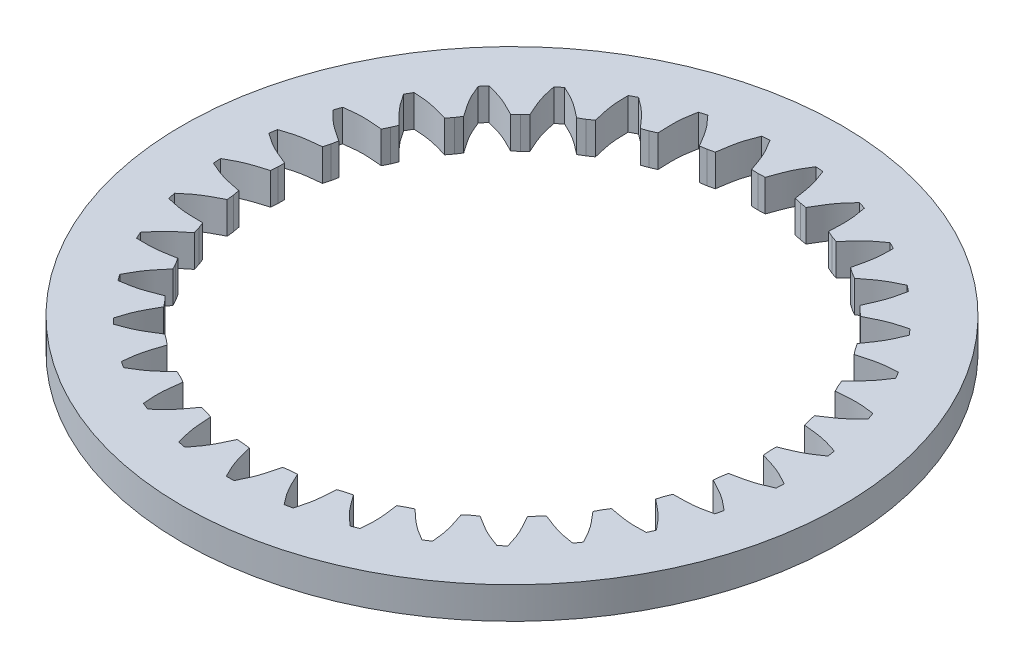
SolidWorks part; units mm, degrees
ref_plane "Plano frontal" through (0, 0, 0) normal (0, 0, 1) x (1, 0, 0)
ref_plane "Plano superior" through (0, 0, 0) normal (0, 1, 0) x (1, 0, 0)
ref_plane "Plano direito" through (0, 0, 0) normal (1, 0, 0) x (0, 0, -1)
sketch "Esboço1" plane through (0, 0, 0) normal (0, 1, 0) x (1, 0, 0)
  line L0 (-38.3259, -48.7353) -> (0, 0)
  line L1 (-39.711, -47.7305) -> (-38.3259, -48.7353)
  line L2 (-38.3259, -48.7353) -> (-37.0229, -49.8445)
  line L3 (-39.1966, -59.1999) -> (-37.5673, -60.247)
  line L4 (-27.2846, -65.5481) -> (-25.4866, -66.2679)
  line L5 (-28.41, -55.1078) -> (-26.9207, -55.9504)
  line L6 (-29.9603, -54.3833) -> (-28.41, -55.1078)
  line L7 (-14.3865, -69.5272) -> (-12.4847, -69.8937)
  line L8 (-17.4674, -59.4886) -> (-15.8455, -60.0341)
  line L9 (-19.1268, -59.0706) -> (-17.4674, -59.4886)
  line L10 (-0.9684, -70.9934) -> (0.9684, -70.9934)
  line L11 (-5.8935, -61.7193) -> (-4.1976, -61.9479)
  line L12 (-7.6019, -61.6229) -> (-5.8935, -61.7193)
  line L13 (12.4847, -69.8937) -> (14.3865, -69.5272)
  line L14 (5.8935, -61.7193) -> (7.6019, -61.6229)
  line L15 (4.1976, -61.9479) -> (5.8935, -61.7193)
  line L16 (25.4866, -66.2679) -> (27.2846, -65.5481)
  line L17 (17.4674, -59.4886) -> (19.1268, -59.0706)
  line L18 (15.8455, -60.0341) -> (17.4674, -59.4886)
  line L19 (37.5673, -60.247) -> (39.1966, -59.1999)
  line L20 (28.41, -55.1078) -> (29.9603, -54.3833)
  line L21 (26.9207, -55.9504) -> (28.41, -55.1078)
  line L22 (48.2902, -52.0486) -> (49.6919, -50.7121)
  line L23 (38.3259, -48.7353) -> (39.711, -47.7305)
  line L24 (37.0229, -49.8445) -> (38.3259, -48.7353)
  line L25 (57.2678, -41.969) -> (58.3912, -40.3914)
  line L26 (46.8565, -40.6014) -> (48.0264, -39.3526)
  line L27 (45.7869, -41.9371) -> (46.8565, -40.6014)
  line L28 (64.1756, -30.3726) -> (64.9801, -28.6109)
  line L29 (53.6936, -31) -> (54.6061, -29.5524)
  line L30 (52.8962, -32.514) -> (53.6936, -31)
  line L31 (68.7639, -17.6784) -> (69.2205, -15.7962)
  line L32 (58.59, -20.2782) -> (59.2121, -18.6841)
  line L33 (58.0936, -21.9158) -> (58.59, -20.2782)
  line L34 (70.8669, -4.3453) -> (70.9591, -2.4107)
  line L35 (61.3689, -8.8235) -> (61.678, -7.1405)
  line L36 (61.1914, -10.5255) -> (61.3689, -8.8235)
  line L37 (70.4086, 9.1449) -> (70.133, 11.0619)
  line L38 (61.9298, 2.9501) -> (61.9148, 4.6612)
  line L39 (62.0775, 1.2453) -> (61.9298, 2.9501)
  line L40 (67.4055, 22.3045) -> (66.7721, 24.1348)
  line L41 (60.2523, 14.6171) -> (59.9138, 16.2944)
  line L42 (60.72, 12.971) -> (60.2523, 14.6171)
  line L43 (61.9663, 34.6581) -> (60.9979, 36.3353)
  line L44 (56.3972, 25.7557) -> (55.7473, 27.3387)
  line L45 (57.1679, 24.228) -> (56.3972, 25.7557)
  line L46 (54.2874, 45.7589) -> (53.0191, 47.2226)
  line L47 (50.5037, 35.9635) -> (49.566, 37.3949)
  line L48 (51.5497, 34.6092) -> (50.5037, 35.9635)
  line L49 (44.6464, 55.206) -> (43.124, 56.4032)
  line L50 (42.7849, 44.8715) -> (41.5932, 46.0996)
  line L51 (44.0683, 43.7396) -> (42.7849, 44.8715)
  line L52 (33.3918, 62.6577) -> (31.6703, 63.5452)
  line L53 (33.5197, 52.1577) -> (32.1172, 53.1381)
  line L54 (34.9941, 51.2892) -> (33.5197, 52.1577)
  line L55 (20.9303, 67.8448) -> (19.072, 68.3905)
  line L56 (23.0431, 57.5588) -> (21.4804, 58.256)
  line L57 (24.6552, 56.985) -> (23.0431, 57.5588)
  line L58 (7.7123, 70.5799) -> (5.7844, 70.764)
  line L59 (11.7336, 60.8796) -> (10.0672, 61.2684)
  line L60 (13.4252, 60.6212) -> (11.7336, 60.8796)
  line L61 (-5.7844, 70.764) -> (-7.7123, 70.5799)
  line L62 (0, 62) -> (-1.7099, 62.0665)
  line L63 (1.7099, 62.0665) -> (0, 62)
  line L64 (-19.072, 68.3905) -> (-20.9303, 67.8448)
  line L65 (-11.7336, 60.8796) -> (-13.4251, 60.6212)
  line L66 (-10.0672, 61.2684) -> (-11.7336, 60.8796)
  line L67 (-31.6703, 63.5452) -> (-33.3918, 62.6577)
  line L68 (-23.0431, 57.5588) -> (-24.6552, 56.985)
  line L69 (-21.4804, 58.256) -> (-23.0431, 57.5588)
  line L70 (-43.124, 56.4032) -> (-44.6464, 55.206)
  line L71 (-33.5197, 52.1577) -> (-34.9941, 51.2892)
  line L72 (-32.1172, 53.1381) -> (-33.5197, 52.1577)
  line L73 (-53.0191, 47.2226) -> (-54.2874, 45.7589)
  line L74 (-42.7849, 44.8715) -> (-44.0683, 43.7396)
  line L75 (-41.5932, 46.0996) -> (-42.7849, 44.8715)
  line L76 (-60.9979, 36.3353) -> (-61.9663, 34.6581)
  line L77 (-50.5037, 35.9635) -> (-51.5497, 34.6092)
  line L78 (-49.566, 37.3949) -> (-50.5037, 35.9635)
  line L79 (-66.7721, 24.1348) -> (-67.4055, 22.3045)
  line L80 (-56.3972, 25.7557) -> (-57.1679, 24.228)
  line L81 (-55.7473, 27.3387) -> (-56.3972, 25.7557)
  line L82 (-70.133, 11.0619) -> (-70.4086, 9.1449)
  line L83 (-60.2523, 14.6171) -> (-60.72, 12.971)
  line L84 (-59.9138, 16.2944) -> (-60.2523, 14.6171)
  line L85 (-70.9591, -2.4107) -> (-70.8669, -4.3453)
  line L86 (-61.9298, 2.9501) -> (-62.0775, 1.2453)
  line L87 (-61.9148, 4.6612) -> (-61.9298, 2.9501)
  line L88 (-69.2205, -15.7962) -> (-68.7639, -17.6784)
  line L89 (-61.3689, -8.8235) -> (-61.1914, -10.5255)
  line L90 (-61.678, -7.1405) -> (-61.3689, -8.8235)
  line L91 (-64.9801, -28.6108) -> (-64.1756, -30.3726)
  line L92 (-58.5901, -20.2782) -> (-58.0936, -21.9158)
  line L93 (-59.2121, -18.6841) -> (-58.5901, -20.2782)
  line L94 (-58.3912, -40.3914) -> (-57.2678, -41.969)
  line L95 (-53.6936, -31) -> (-52.8962, -32.514)
  line L96 (-54.6061, -29.5524) -> (-53.6936, -31)
  line L97 (-49.6919, -50.7121) -> (-48.2902, -52.0486)
  line L98 (-46.8565, -40.6014) -> (-45.787, -41.9371)
  line L99 (-48.0264, -39.3526) -> (-46.8565, -40.6014)
  circle A0 centre (0, 0) radius 83
  spline S0 degree 3 number of poles 788 (-39.1966, -59.1999) -> (-37.0229, -49.8445)
  spline S1 degree 3 number of poles 788 (-48.2902, -52.0486) -> (-39.711, -47.7305)
  spline S2 degree 3 number of poles 788 (-27.2846, -65.5481) -> (-26.9207, -55.9504)
  spline S3 degree 3 number of poles 788 (-37.5673, -60.247) -> (-29.9603, -54.3833)
  spline S4 degree 3 number of poles 788 (-14.3865, -69.5272) -> (-15.8455, -60.0341)
  spline S5 degree 3 number of poles 788 (-25.4866, -66.2679) -> (-19.1268, -59.0706)
  spline S6 degree 3 number of poles 788 (-0.9684, -70.9934) -> (-4.1976, -61.9479)
  spline S7 degree 3 number of poles 788 (-12.4847, -69.8937) -> (-7.6019, -61.6229)
  spline S8 degree 3 number of poles 788 (12.4847, -69.8937) -> (7.6019, -61.6229)
  spline S9 degree 3 number of poles 788 (0.9684, -70.9934) -> (4.1976, -61.9479)
  spline S10 degree 3 number of poles 788 (25.4866, -66.2679) -> (19.1268, -59.0706)
  spline S11 degree 3 number of poles 788 (14.3865, -69.5272) -> (15.8455, -60.0341)
  spline S12 degree 3 number of poles 788 (37.5673, -60.247) -> (29.9603, -54.3833)
  spline S13 degree 3 number of poles 788 (27.2846, -65.5481) -> (26.9207, -55.9504)
  spline S14 degree 3 number of poles 788 (48.2902, -52.0486) -> (39.711, -47.7305)
  spline S15 degree 3 number of poles 788 (39.1966, -59.1999) -> (37.0229, -49.8445)
  spline S16 degree 3 number of poles 788 (57.2678, -41.969) -> (48.0264, -39.3526)
  spline S17 degree 3 number of poles 788 (49.6919, -50.7121) -> (45.7869, -41.9371)
  spline S18 degree 3 number of poles 788 (64.1756, -30.3726) -> (54.6061, -29.5524)
  spline S19 degree 3 number of poles 788 (58.3912, -40.3914) -> (52.8962, -32.514)
  spline S20 degree 3 number of poles 788 (68.7639, -17.6784) -> (59.2121, -18.6841)
  spline S21 degree 3 number of poles 788 (64.9801, -28.6109) -> (58.0936, -21.9158)
  spline S22 degree 3 number of poles 788 (70.8669, -4.3453) -> (61.678, -7.1405)
  spline S23 degree 3 number of poles 788 (69.2205, -15.7962) -> (61.1914, -10.5255)
  spline S24 degree 3 number of poles 788 (70.4086, 9.1449) -> (61.9148, 4.6612)
  spline S25 degree 3 number of poles 788 (70.9591, -2.4107) -> (62.0775, 1.2453)
  spline S26 degree 3 number of poles 788 (67.4055, 22.3045) -> (59.9138, 16.2944)
  spline S27 degree 3 number of poles 788 (70.133, 11.0619) -> (60.72, 12.971)
  spline S28 degree 3 number of poles 788 (61.9663, 34.6581) -> (55.7473, 27.3387)
  spline S29 degree 3 number of poles 788 (66.7721, 24.1348) -> (57.1679, 24.228)
  spline S30 degree 3 number of poles 788 (54.2874, 45.7589) -> (49.566, 37.3949)
  spline S31 degree 3 number of poles 788 (60.9979, 36.3353) -> (51.5497, 34.6092)
  spline S32 degree 3 number of poles 788 (44.6464, 55.206) -> (41.5932, 46.0996)
  spline S33 degree 3 number of poles 788 (53.0191, 47.2226) -> (44.0683, 43.7396)
  spline S34 degree 3 number of poles 788 (33.3918, 62.6577) -> (32.1172, 53.1381)
  spline S35 degree 3 number of poles 788 (43.124, 56.4032) -> (34.9941, 51.2892)
  spline S36 degree 3 number of poles 788 (20.9303, 67.8448) -> (21.4804, 58.256)
  spline S37 degree 3 number of poles 788 (31.6703, 63.5452) -> (24.6552, 56.985)
  spline S38 degree 3 number of poles 788 (7.7123, 70.5799) -> (10.0672, 61.2684)
  spline S39 degree 3 number of poles 788 (19.072, 68.3905) -> (13.4252, 60.6212)
  spline S40 degree 3 number of poles 788 (-5.7844, 70.764) -> (-1.7099, 62.0665)
  spline S41 degree 3 number of poles 788 (5.7844, 70.764) -> (1.7099, 62.0665)
  spline S42 degree 3 number of poles 788 (-19.072, 68.3905) -> (-13.4251, 60.6212)
  spline S43 degree 3 number of poles 788 (-7.7123, 70.5799) -> (-10.0672, 61.2684)
  spline S44 degree 3 number of poles 788 (-31.6703, 63.5452) -> (-24.6552, 56.985)
  spline S45 degree 3 number of poles 788 (-20.9303, 67.8448) -> (-21.4804, 58.256)
  spline S46 degree 3 number of poles 788 (-43.124, 56.4032) -> (-34.9941, 51.2892)
  spline S47 degree 3 number of poles 788 (-33.3918, 62.6577) -> (-32.1172, 53.1381)
  spline S48 degree 3 number of poles 788 (-53.0191, 47.2226) -> (-44.0683, 43.7396)
  spline S49 degree 3 number of poles 788 (-44.6464, 55.206) -> (-41.5932, 46.0996)
  spline S50 degree 3 number of poles 788 (-60.9979, 36.3353) -> (-51.5497, 34.6092)
  spline S51 degree 3 number of poles 788 (-54.2874, 45.7589) -> (-49.566, 37.3949)
  spline S52 degree 3 number of poles 788 (-66.7721, 24.1348) -> (-57.1679, 24.228)
  spline S53 degree 3 number of poles 788 (-61.9663, 34.6581) -> (-55.7473, 27.3387)
  spline S54 degree 3 number of poles 788 (-70.133, 11.0619) -> (-60.72, 12.971)
  spline S55 degree 3 number of poles 788 (-67.4055, 22.3045) -> (-59.9138, 16.2944)
  spline S56 degree 3 number of poles 788 (-70.9591, -2.4107) -> (-62.0775, 1.2453)
  spline S57 degree 3 number of poles 788 (-70.4086, 9.1449) -> (-61.9148, 4.6612)
  spline S58 degree 3 number of poles 788 (-69.2205, -15.7962) -> (-61.1914, -10.5255)
  spline S59 degree 3 number of poles 788 (-70.8669, -4.3453) -> (-61.678, -7.1405)
  spline S60 degree 3 number of poles 788 (-64.9801, -28.6108) -> (-58.0936, -21.9158)
  spline S61 degree 3 number of poles 788 (-68.7639, -17.6784) -> (-59.2121, -18.6841)
  spline S62 degree 3 number of poles 788 (-58.3912, -40.3914) -> (-52.8962, -32.514)
  spline S63 degree 3 number of poles 788 (-64.1756, -30.3726) -> (-54.6061, -29.5524)
  spline S64 degree 3 number of poles 788 (-49.6919, -50.7121) -> (-45.787, -41.9371)
  spline S65 degree 3 number of poles 788 (-57.2678, -41.969) -> (-48.0264, -39.3526)
  point P303 (0, 0)
  dimension "D1" = 33
extrude "Ressalto-extrusão1" add sketch "Esboço1" along normal blind 8 contours A0 S65 L94 S62 L95 L96 S63 L91 S60 L92 L93 S61 L88 S58 L89 L90 S59 L85 S56 L86 L87 S57 L82 S54 L83 L84 S55 L79 S52 L80 L81 S53 L76 S50 L77 L78 S51 L73 S48 L74 L75 S49 L70 S46 L71 L72 S47 L67 S44 L68 region at (-80.6524, 0, 0)
